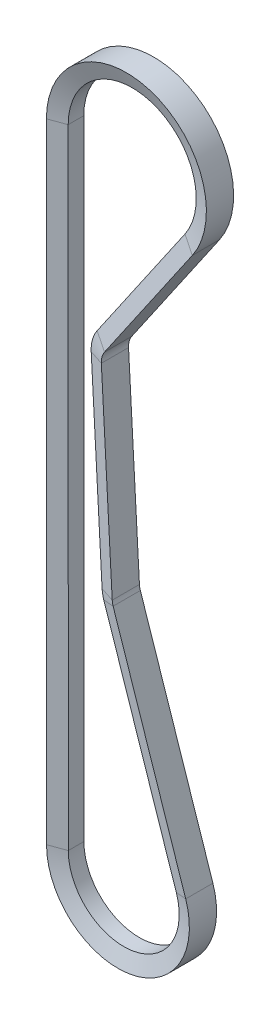
SolidWorks part; units mm, degrees
ref_plane "Front Plane" through (0, 0, 0) normal (0, 0, 1) x (1, 0, 0)
ref_plane "Top Plane" through (0, 0, 0) normal (0, 1, 0) x (1, 0, 0)
ref_plane "Right Plane" through (0, 0, 0) normal (1, 0, 0) x (0, 0, -1)
sketch "Sketch2" plane through (0, 0, 0) normal (0, 0, 1) x (1, 0, 0)
  line L0 (0, 0) -> (1, 0) construction
  line L1 (0, 0) -> (0, 1) construction
  line L12 (-25, -0.0049) -> (-25.0427, 219.9747)
  line L14 (26.0246, 204.1088) -> (-4.7057, 159.4454)
  line L15 (-5.815, 155.5007) -> (-2.0083, 85.6043)
  line L16 (-1.6903, 83.937) -> (23.7111, 7.9235)
  arc A4 (-25.0427, 219.9747) -> (26.0246, 204.1088) centre (2.9573, 219.9801) cw
  arc A7 (23.7111, 7.9235) -> (-25, -0.0049) centre (0, 0) cw
  arc A8 (-4.7057, 159.4454) -> (-5.815, 155.5007) centre (0.5256, 155.846) ccw
  arc A9 (-2.0083, 85.6043) -> (-1.6903, 83.937) centre (4.3323, 85.9496) ccw
ref_plane "Plane4" through (23.7111, 7.9235, 0) normal (0.3169, -0.9484, 0) x (-0.9484, -0.3169, 0)
sketch "Sketch3" plane through (23.7111, 7.9235, 0) normal (0.3169, -0.9484, 0) x (-0.9484, -0.3169, 0)
  line L0 (0, -4.7625) -> (0, 4.7625)
  line L1 (0, -4.7625) -> (5.588, -2.7286)
  line L2 (5.588, -2.7286) -> (5.588, 2.7286)
  line L3 (5.588, 2.7286) -> (0, 4.7625)
  line L4 (0, 0) -> (5.588, 0) construction
  dimension "D1" = 9.525
  dimension "D2" = 5.588
  dimension "D3" = 40
sweep "Sweep1" add profiles "Sketch3" path "Sketch2"
